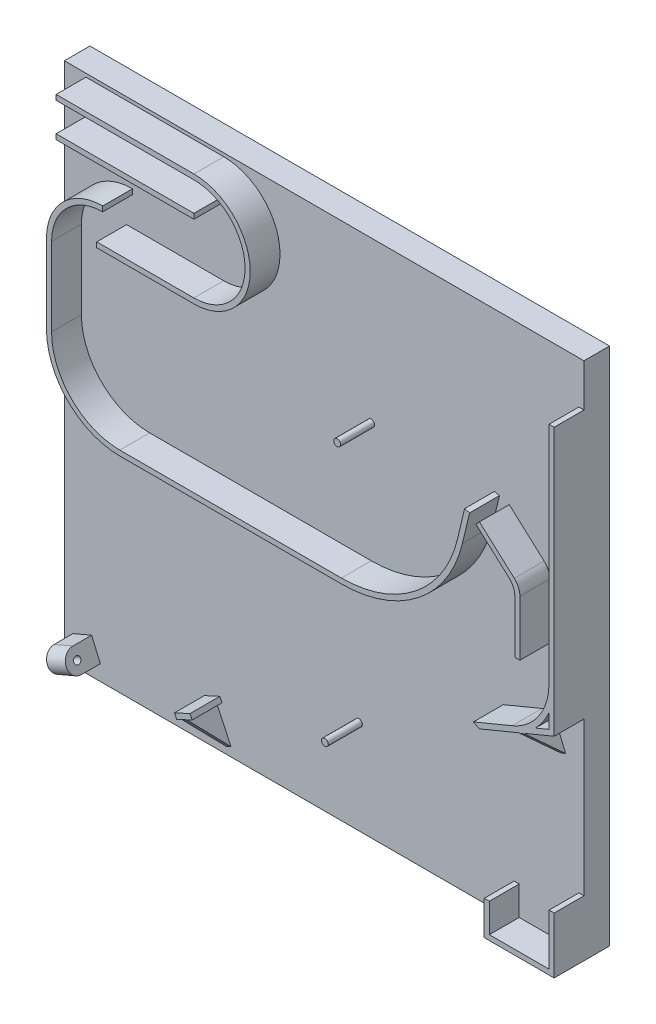
SolidWorks part; units mm, degrees
ref_plane "Front Plane" through (0, 0, 0) normal (0, 0, 1) x (1, 0, 0)
ref_plane "Top Plane" through (0, 0, 0) normal (0, 1, 0) x (1, 0, 0)
ref_plane "Right Plane" through (0, 0, 0) normal (1, 0, 0) x (0, 0, -1)
sketch "Sketch2" plane through (0, 0, 0) normal (0, 0, 1) x (1, 0, 0)
  line L0 (0, 282.8) -> (93.5, 282.8)
  line L1 (0, 0) -> (304.8, 0)
  line L2 (0, 0) -> (0, 304.8)
  line L3 (0, 304.8) -> (304.8, 304.8)
  line L4 (304.8, 0) -> (304.8, 304.8)
  line L5 (93.5, 282.8) -> (93.5, 279.8)
  line L6 (93.5, 279.8) -> (0, 279.8)
  line L7 (0, 299.8) -> (93.5, 299.8)
  line L8 (93.5, 299.8) -> (93.5, 302.8)
  line L9 (93.5, 302.8) -> (0, 302.8)
  line L10 (93.5, 239.8) -> (36.5, 239.8)
  line L11 (93.5, 236.8) -> (36.5, 236.8)
  line L12 (36.5, 236.8) -> (36.5, 239.8)
  line L13 (40, 256.8) -> (40, 259.8)
  line L14 (10, 226.8) -> (10, 180.8)
  line L15 (7, 226.8) -> (7, 180.8)
  line L16 (7, 180.8) -> (10, 180.8)
  line L17 (50.0112, 140.7888) -> (50.0112, 137.7888)
  line L18 (50.0112, 140.7888) -> (180.0112, 140.7888)
  line L19 (180.0112, 140.7888) -> (180.0112, 137.7888)
  line L20 (180.0112, 137.7888) -> (50.0112, 137.7888)
  line L21 (248.1278, 194.6604) -> (251.0471, 193.9692)
  line L22 (180.0112, 210.7888) -> (180.0112, 140.7888) construction
  line L23 (248.1278, 194.6604) -> (180.0112, 210.7888) construction
  line L24 (93.5, 236.8) -> (93.5, 239.8)
  line L25 (304.8, 279.8) -> (301.8, 279.8)
  line L26 (301.8, 279.8) -> (301.8, 148.1863)
  line L27 (301.8, 124.8) -> (304.8, 124.8)
  line L28 (251.0471, 193.9692) -> (255.1944, 211.4849)
  line L29 (248.1278, 194.6604) -> (252.2751, 212.1761)
  line L30 (252.2751, 212.1761) -> (255.1944, 211.4849)
  line L31 (284.7336, 151.3878) -> (284.7336, 183.9355)
  line L32 (281.4249, 191.367) -> (260.953, 209.8)
  line L33 (284.7336, 151.3878) -> (281.7336, 151.3878)
  line L34 (281.7336, 151.3878) -> (281.7336, 182.5998)
  line L35 (260.953, 209.8) -> (258.9456, 207.5706)
  line L36 (258.9456, 207.5706) -> (278.4249, 190.0313)
  line L37 (280.1939, 115.8505) -> (257.4538, 106.4312)
  line L38 (257.4538, 106.4312) -> (0.5061, 0) construction
  line L39 (260.953, 104.6334) -> (304.8, 122.7955)
  line L40 (301.8, 124.8) -> (301.8, 148.1863)
  line L41 (280.1939, 115.8505) -> (301.8, 124.8)
  line L42 (257.4538, 106.4312) -> (260.953, 104.6334)
  line L43 (304.8, 33) -> (301.8, 33)
  line L44 (301.8, 33) -> (301.8, 3)
  line L45 (301.8, 3) -> (266.8, 3)
  line L46 (266.8, 3) -> (266.8, 20)
  line L47 (266.8, 20) -> (263.8, 20)
  line L48 (263.8, 20) -> (263.8, 0)
  line L49 (95, 0) -> (95, 4) construction
  line L50 (95, 4) -> (86.5476, 22.1262)
  line L51 (86.5476, 22.1262) -> (89.2666, 23.394)
  line L52 (89.2666, 23.394) -> (97.7189, 5.2679)
  line L53 (97.7189, 5.2679) -> (95, 4)
  line L54 (89.2666, 23.394) -> (92.4386, 24.8732)
  line L55 (86.5476, 22.1262) -> (83.3756, 20.647)
  line L56 (83.3756, 20.647) -> (82.1263, 23.3745)
  line L57 (82.1263, 23.3745) -> (91.1997, 27.5301)
  line L58 (91.1997, 27.5301) -> (92.4386, 24.8732)
  line L59 (304.8, 55) -> (172.8, 55) construction
  line L60 (21.1078, 279.8) -> (21.1078, 263.8)
  line L61 (5, 16.3) -> (16, 21)
  line L62 (16, 21) -> (21.1078, 9.0455)
  line L63 (21.1078, 9.0455) -> (10.1078, 4.3455)
  line L64 (10.1078, 4.3455) -> (5, 16.3)
  line L65 (21.1078, 263.8) -> (24.1078, 263.8)
  line L66 (24.1078, 263.8) -> (24.1078, 279.8)
  line L67 (46.3418, 236.8) -> (46.3418, 219.3)
  line L68 (46.3418, 219.3) -> (49.3418, 219.3)
  line L69 (49.3418, 219.3) -> (49.3418, 236.8)
  line L70 (112.8536, 137.7888) -> (112.8536, 121.7888)
  line L71 (112.8536, 121.7888) -> (115.8536, 121.7888)
  line L72 (115.8536, 121.7888) -> (115.8536, 137.7888)
  line L73 (284.7336, 114.4837) -> (291.2392, 98.7777)
  line L74 (291.2392, 98.7777) -> (294.0109, 99.9258)
  line L75 (294.0109, 99.9258) -> (287.5053, 115.6317)
  arc A0 (93.5, 299.8) -> (93.5, 239.8) centre (93.5, 269.8) cw
  arc A1 (93.5, 302.8) -> (93.5, 236.8) centre (93.5, 269.8) cw
  arc A2 (40, 256.8) -> (10, 226.8) centre (40, 226.8) ccw
  arc A3 (40, 259.8) -> (7, 226.8) centre (40, 226.8) ccw
  arc A4 (10, 180.8) -> (50.0112, 140.7888) centre (50.0112, 180.8) ccw
  arc A5 (7, 180.8) -> (50.0112, 137.7888) centre (50.0112, 180.8) ccw
  arc A6 (180.0112, 140.7888) -> (248.1278, 194.6604) centre (180.0112, 210.7888) ccw
  arc A7 (180.0112, 137.7888) -> (251.0471, 193.9692) centre (180.0112, 210.7888) ccw
  circle A8 centre (180.0112, 210.7888) radius 2
  arc A9 (278.4249, 190.0313) -> (281.7336, 182.5998) centre (271.7336, 182.5998) cw
  arc A10 (281.4249, 191.367) -> (284.7336, 183.9355) centre (274.7336, 183.9355) cw
  arc A11 (280.1939, 115.8505) -> (301.8, 148.1863) centre (266.8, 148.1863) ccw
  arc A12 (301.8, 133.3876) -> (293.8661, 121.5137) centre (266.8, 148.1863) cw
  circle A13 centre (172.8, 55) radius 2
  point P52 (281.7336, 187.0521)
  point P55 (284.7336, 188.3878)
  dimension "D8" = 30
  dimension "D9" = 33
  dimension "D13" = 30
  dimension "D15" = 3
  dimension "D20" = 40.0112
  dimension "D21" = 43.0112
  dimension "D23" = 70
  dimension "D24" = 73
  dimension "D26" = 4
  dimension "D28" = 43
  dimension "D39" = 3
  dimension "D43" = 10
  dimension "D47" = 35
  dimension "D48" = 3
  dimension "D72" = 4
  dimension "D1" = 304.8
  dimension "D2" = 304.8
  dimension "D3" = 3
  dimension "D4" = 22
  dimension "D5" = 93.5
  dimension "D6" = 3
  dimension "D7" = 2
  dimension "D10" = 57
  dimension "D11" = 25
  dimension "D12" = 10
  dimension "D14" = 17
  dimension "D16" = 3
  dimension "D17" = 124
  dimension "D18" = 46
  dimension "D19" = 3
  dimension "D22" = 130
  dimension "D25" = 18
  dimension "D27" = 76.679
  dimension "D29" = 155
  dimension "D30" = 25
  dimension "D31" = 3
  dimension "D32" = 132
  dimension "D33" = 3
  dimension "D34" = 95
  dimension "D35" = 32
  dimension "D36" = 6
  dimension "D37" = 17.0664
  dimension "D38" = 37
  dimension "D40" = 3
  dimension "D41" = 3
  dimension "D42" = 3
  dimension "D44" = 48
  dimension "D45" = 112.5
  dimension "D46" = 3
  dimension "D49" = 3
  dimension "D50" = 3
  dimension "D51" = 3
  dimension "D52" = 33
  dimension "D53" = 35
  dimension "D54" = 17
  dimension "D55" = 95
  dimension "D56" = 4
  dimension "D57" = 3
  dimension "D58" = 20
  dimension "D59" = 10
  dimension "D60" = 3.5
  dimension "D61" = 3
  dimension "D62" = 65
  dimension "D63" = 21
  dimension "D64" = 16.3
  dimension "D65" = 11
  dimension "D66" = 5
  dimension "D67" = 13
  dimension "D68" = 90
  dimension "D69" = 2.9316
  dimension "D70" = 132
  dimension "D71" = 55
  dimension "D73" = 16
  dimension "D74" = 3
  dimension "D75" = 3
  dimension "D76" = 17.5
  dimension "D77" = 3
  dimension "D78" = 16
  dimension "D79" = 3
  dimension "D80" = 17
  dimension "D81" = 46.6056
  dimension "D82" = 63.2986
extrude "Boss-Extrude1" add sketch "Sketch2" against normal blind 15 contours L37 A11 L26 L25 L4 L3 L2 L9 A1 L11 L69 L68 L67 L12 L10 A0 L7 L0 L5 L6 L66 L65 L60 L1 L48 L47 L46 L45 L44 L43 L39 L75 L74 L73 L42 A13 L32 A10 L31 L33 L34 A9 L36 | L65 L66 L6 L60 | L6 L5 L0 L2 | L8 L9 L2 L7 | A1 L8 A0 L24 | L11 L24 L10 L12 | L68 L69 L11 L67 | L13 A3 L15 L16 L14 A2 | L16 A5 L17 A4 | L20 L19 L18 L17 | L71 L72 L20 L70 | A8 | L19 A7 L21 A6 | L30 L29 L21 L28 | A10 L32 L35 L36 A9 L34 L33 L31 | L40 L27 L4 L25 L26 | A12 L40 A11 L41 | L40 A12 L41 | L37 L42 L39 L4 L27 L41 | L74 L75 L39 L73 | L47 L48 L1 L4 L43 L44 L45 L46 | L58 L57 L56 L55 L51 L54 | L53 L52 L51 L50 | L64 L63 L62 L61 | A13 region at (152.5011, 151.231, 0) region at (46.75, 281.3, 0) region at (46.75, 301.3, 0) region at (22.6078, 271.8, 0) region at (94.2379, 301.3, 0) region at (264.3263, 10, 0) region at (65, 238.3, 0) region at (303.3, 202.3, 0) region at (47.8418, 228.05, 0) region at (281.7124, 114.8615, 0) region at (289.3723, 107.2047, 0) region at (299.4119, 126.3957, 0) region at (296.3291, 128.4556, 0) region at (18.1814, 248.6186, 0) region at (21.2889, 152.0777, 0) region at (115.0112, 139.2888, 0) region at (223.9981, 155.1707, 0) region at (114.3536, 129.7888, 0) region at (251.6611, 203.0726, 0) region at (283.2336, 152.0263, 0) region at (92.1333, 13.697, 0) region at (87.2678, 24.0977, 0) region at (13.0539, 12.6728, 0) region at (180.0112, 210.7888, 0) region at (172.8, 55, 0)
extrude "Boss-Extrude2" add sketch "Sketch2<3>" along normal blind 17.5 contours L6 L5 L0 L2 | L13 A3 L15 L16 L14 A2 | L11 L24 L10 L12 | A1 L8 A0 L24 | L8 L9 L2 L7 | L16 A5 L17 A4 | L20 L19 L18 L17 | L19 A7 L21 A6 | L30 L29 L21 L28 | A10 L32 L35 L36 A9 L34 L33 L31 | L40 L27 L4 L25 L26 | A12 L40 A11 L41 | L37 L42 L39 L4 L27 L41 | L47 L48 L1 L4 L43 L44 L45 L46 | L58 L57 L56 L55 L51 L54 | L65 L66 L6 L60 | L68 L69 L11 L67 | L71 L72 L20 L70 | L74 L75 L39 L73 | L64 L63 L62 L61 | L53 L52 L51 L50 region at (46.75, 281.3, 0) region at (46.75, 301.3, 0) region at (22.6078, 271.8, 0) region at (94.2379, 301.3, 0) region at (264.3263, 10, 0) region at (65, 238.3, 0) region at (303.3, 202.3, 0) region at (47.8418, 228.05, 0) region at (281.7124, 114.8615, 0) region at (289.3723, 107.2047, 0) region at (296.3291, 128.4556, 0) region at (18.1814, 248.6186, 0) region at (21.2889, 152.0777, 0) region at (115.0112, 139.2888, 0) region at (223.9981, 155.1707, 0) region at (114.3536, 129.7888, 0) region at (251.6611, 203.0726, 0) region at (283.2336, 152.0263, 0) region at (92.1333, 13.697, 0) region at (87.2678, 24.0977, 0) region at (13.0539, 12.6728, 0)
sketch "Sketch2<3>" plane through (0, 0, 0) normal (0, 0, 1) x (1, 0, 0) same geometry as "Sketch2"
sketch "Sketch3" plane through (79.5645, 37.1015, 0) normal (-0.9063, -0.4226, 0) x (0, 0, 1)
  line L0 (17.5, -16.5235) -> (0, -36.5235)
  line L1 (0, -36.5235) -> (17.5, -36.5235)
  line L2 (17.5, -36.5235) -> (17.5, -16.5235)
extrude "Cut-Extrude1" cut sketch "Sketch3" against normal blind 17.5
sketch "Sketch4" plane through (283.5114, 117.4343, 0) normal (-0.9239, -0.3827, 0) x (0, 0, 1)
  line L0 (17.5, -3.4526) -> (0, -20.1937)
  line L1 (17.5, -3.1937) -> (17.5, -20.1937) construction
  line L2 (17.5, -20.1937) -> (0, -20.1937) construction
  line L3 (0, -20.1937) -> (17.5, -20.1937)
  line L4 (17.5, -20.1937) -> (17.5, -3.4526)
extrude "Cut-Extrude2" cut sketch "Sketch4" against normal blind 17.5
sketch "Sketch5" plane through (112.8536, 0, 0) normal (-1, 0, 0) x (0, 0, 1)
  line L0 (17.5, 137.7888) -> (17.5, 121.7888)
  line L1 (17.5, 137.7888) -> (17.5, 121.7888) construction
  line L2 (17.5, 121.7888) -> (0, 121.7888)
  line L3 (0, 121.7888) -> (17.5, 137.7888)
extrude "Cut-Extrude3" cut sketch "Sketch5" against normal blind 17.5
sketch "Sketch6" plane through (46.3418, 0, 0) normal (-1, 0, 0) x (0, 0, 1)
  line L0 (17.5, 236.8) -> (17.5, 219.3)
  line L1 (17.5, 219.3) -> (0, 219.3)
  line L2 (0, 219.3) -> (17.5, 236.8)
extrude "Cut-Extrude4" cut sketch "Sketch6" against normal blind 17.5
sketch "Sketch7" plane through (21.1078, 0, 0) normal (-1, 0, 0) x (0, 0, 1)
  line L0 (17.5, 279.8) -> (0, 263.8)
  line L1 (0, 263.8) -> (17.5, 263.8)
  line L2 (17.5, 263.8) -> (17.5, 279.8)
extrude "Cut-Extrude5" cut sketch "Sketch7" against normal blind 17.5
extrude "Boss-Extrude3" add sketch "Sketch2<5>" along normal blind 20 contours A13 | A8 region at (172.8, 55, 0)
sketch "Sketch2<5>" plane through (0, 0, 0) normal (0, 0, 1) x (1, 0, 0) same geometry as "Sketch2"
sketch "Sketch8" plane through (0, 0, -15) normal (0, 0, -1) x (-1, 0, 0)
  line L0 (-162.4, 0) -> (-162.4, 95)
  line L1 (0, 0) -> (-304.8, 0) construction
  line L2 (-162.4, 95) -> (-142.4, 95)
  line L3 (-142.4, 95) -> (-142.4, 0)
  line L6 (0, 0) -> (0, 304.8) construction
  line L11 (-304.8, 0) -> (0, 0)
  line L12 (0, 0) -> (0, 304.8)
  line L13 (0, 304.8) -> (-304.8, 304.8)
  line L14 (-304.8, 304.8) -> (-304.8, 0)
  line L15 (-162.4, 0) -> (-142.4, 0)
  dimension "D1" = 20
  dimension "D2" = 142.4
  dimension "D3" = 95
  dimension "D4" = 0
extrude "Boss-Extrude4" add sketch "Sketch8" along normal blind 45
sketch "Sketch9" plane through (162.4, 0, 0) normal (1, 0, 0) x (0, 0, -1)
  line L0 (45.9914, 95) -> (60, 95)
  line L1 (60, 95) -> (15, 95) construction
  line L2 (60, 95) -> (60, 0)
  line L3 (60, 0) -> (45.9914, 95)
extrude "Cut-Extrude6" cut sketch "Sketch9" against normal blind 45
sketch "Sketch11" plane through (0, 279.8, 0) normal (0, -1, 0) x (1, 0, 0)
  line L0 (0, 17.5) -> (12.6814, 17.5)
  line L1 (21.1078, 17.5) -> (0, 17.5) construction
  line L2 (12.6814, 17.5) -> (12.6814, 0)
  line L3 (21.1078, 0) -> (0, 0) construction
  line L4 (12.6814, 0) -> (0, 0)
  line L5 (0, 0) -> (0, 17.5)
extrude "Cut-Extrude8" cut sketch "Sketch11" against normal blind 35
sketch "Sketch10" plane through (10.1175, 4.3229, 0) normal (-0.9196, -0.3929, 0) x (0, 0, 1)
  line L0 (0, 13.0246) -> (11, 13.0246)
  line L1 (17.5, 6.5246) -> (17.5, 0.0246)
  line L2 (17.5, 0.0246) -> (0, 0.0246)
  line L3 (0, 0.0246) -> (0, 13.0246)
  arc A0 (11, 13.0246) -> (11, 0.0246) centre (11, 6.5246) cw
  circle A1 centre (11, 6.5246) radius 2
  point P10 (17.5, 13.0246)
  point P12 (11, 6.5246)
  line M3 (17.5, 0.0246) -> (17.5, 13.0246)
  line M4 (17.5, 13.0246) -> (0, 13.0246)
extrude "Cut-Extrude7" cut sketch "Sketch10" against normal blind 45 contours A1 | A0 M4 M3 | A0 L2 M3 region at (5.5705, 14.9649, 16.0481) region at (9.5374, 5.6806, 16.0481) region at (7.5539, 10.3228, 11)
